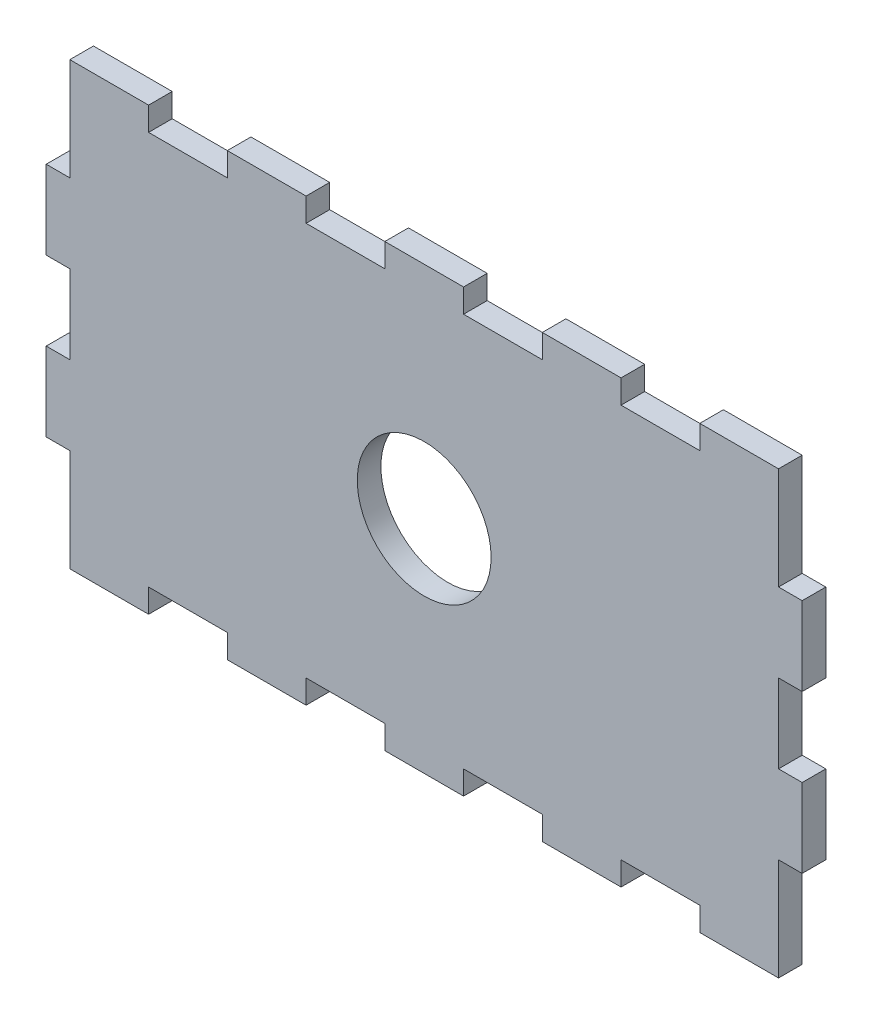
SolidWorks part; units mm, degrees
ref_plane "Front Plane" through (0, 0, 0) normal (0, 0, 1) x (1, 0, 0)
ref_plane "Top Plane" through (0, 0, 0) normal (0, 1, 0) x (1, 0, 0)
ref_plane "Right Plane" through (0, 0, 0) normal (1, 0, 0) x (0, 0, -1)
sketch "Sketch1" plane through (0, 0, 0) normal (0, 0, 1) x (1, 0, 0)
  line L0 (25, 28) -> (25, 25)
  line L1 (-46.5, 26.5) -> (46.5, 26.5) construction
  line L2 (-46.5, 26.5) -> (-46.5, -26.5) construction
  line L3 (-46.5, -26.5) -> (46.5, -26.5) construction
  line L4 (46.5, 26.5) -> (46.5, -26.5) construction
  line L5 (-46.5, 26.5) -> (46.5, -26.5) construction
  line L6 (-46.5, -26.5) -> (46.5, 26.5) construction
  line L7 (-5, 28) -> (5, 28)
  line L8 (-5, 28) -> (-5, 25)
  line L9 (-5, 25) -> (5, 25) construction
  line L10 (5, 28) -> (5, 25)
  line L11 (-5, 28) -> (5, 25) construction
  line L12 (-5, 25) -> (5, 28) construction
  line L13 (15, 28) -> (25, 28)
  line L14 (15, 28) -> (15, 25)
  line L15 (45, 28) -> (45, 25)
  line L16 (35, 28) -> (45, 28)
  line L17 (35, 28) -> (35, 25)
  line L18 (-15, 28) -> (-15, 25)
  line L19 (-25, 28) -> (-15, 28)
  line L20 (-25, 28) -> (-25, 25)
  line L21 (-35, 28) -> (-35, 25)
  line L22 (-45, 28) -> (-35, 28)
  line L23 (0, 0) -> (8.5024, 0) construction
  line L24 (-45, 28) -> (-45, 25)
  line L25 (-35, 25) -> (-25, 25)
  line L26 (-15, 25) -> (-5, 25)
  line L27 (5, 25) -> (15, 25)
  line L28 (0, 0) -> (0, 11.5614) construction
  line L29 (25, 25) -> (35, 25)
  line L30 (-48, 5) -> (-48, 15)
  line L31 (-48, -15) -> (-45, -15)
  line L32 (-45, -15) -> (-45, -25)
  line L33 (-48, -15) -> (-48, -5)
  line L34 (45, -28) -> (45, -25)
  line L35 (35, -28) -> (45, -28)
  line L36 (35, -28) -> (35, -25)
  line L37 (25, -25) -> (35, -25)
  line L38 (25, -28) -> (25, -25)
  line L39 (15, -28) -> (15, -25)
  line L40 (15, -28) -> (25, -28)
  line L41 (5, -25) -> (15, -25)
  line L42 (5, -28) -> (5, -25)
  line L43 (-5, -28) -> (5, -28)
  line L44 (-5, -28) -> (-5, -25)
  line L45 (-15, -25) -> (-5, -25)
  line L46 (-15, -28) -> (-15, -25)
  line L47 (-25, -28) -> (-15, -28)
  line L48 (-48, 5) -> (-45, 5)
  line L49 (-48, 5) -> (-48, -5) construction
  line L50 (-48, -5) -> (-45, -5)
  line L51 (-45, 5) -> (-45, -5)
  line L52 (-48, 5) -> (-45, -5) construction
  line L53 (-48, -5) -> (-45, 5) construction
  line L54 (-45, 25) -> (-45, 15)
  line L55 (-48, 15) -> (-45, 15)
  line L56 (-48, 25) -> (-45, 25) [skipped]
  line L57 (-25, -28) -> (-25, -25)
  line L58 (-35, -28) -> (-35, -25)
  line L59 (-35, -25) -> (-25, -25)
  line L60 (-45, -28) -> (-35, -28)
  line L61 (45, -15) -> (45, -25)
  line L62 (48, -15) -> (45, -15)
  line L63 (48, -15) -> (48, -5)
  line L64 (48, -5) -> (45, -5)
  line L65 (45, 5) -> (45, -5)
  line L66 (48, 5) -> (45, 5)
  line L67 (-48, -25) -> (-45, -25) [skipped]
  line L68 (48, 5) -> (48, 15)
  line L69 (48, 15) -> (45, 15)
  line L70 (45, 25) -> (45, 15)
  line L71 (-45, -28) -> (-45, -25)
  point P0 (0, 0)
  point P6 (0, 26.5)
  point P50 (-46.5, 0)
  dimension "D1" = 93
  dimension "D2" = 53
  dimension "D3" = 10
  dimension "D4" = 3
  dimension "D8" = 3
  dimension "D9" = 10
  dimension "D10" = 3
  dimension "D7" = 3
  dimension "D11" = 2
  dimension "D5" = 2
extrude "Boss-Extrude1" add sketch "Sketch1" along normal blind 3
sketch "Sketch2" plane through (0, 0, 3) normal (0, 0, 1) x (1, 0, 0)
  circle A0 centre (0, 0) radius 8.5
  point P0 (0, 0)
  dimension "D1" = 17
extrude "Cut-Extrude1" cut sketch "Sketch2" against normal blind 3
